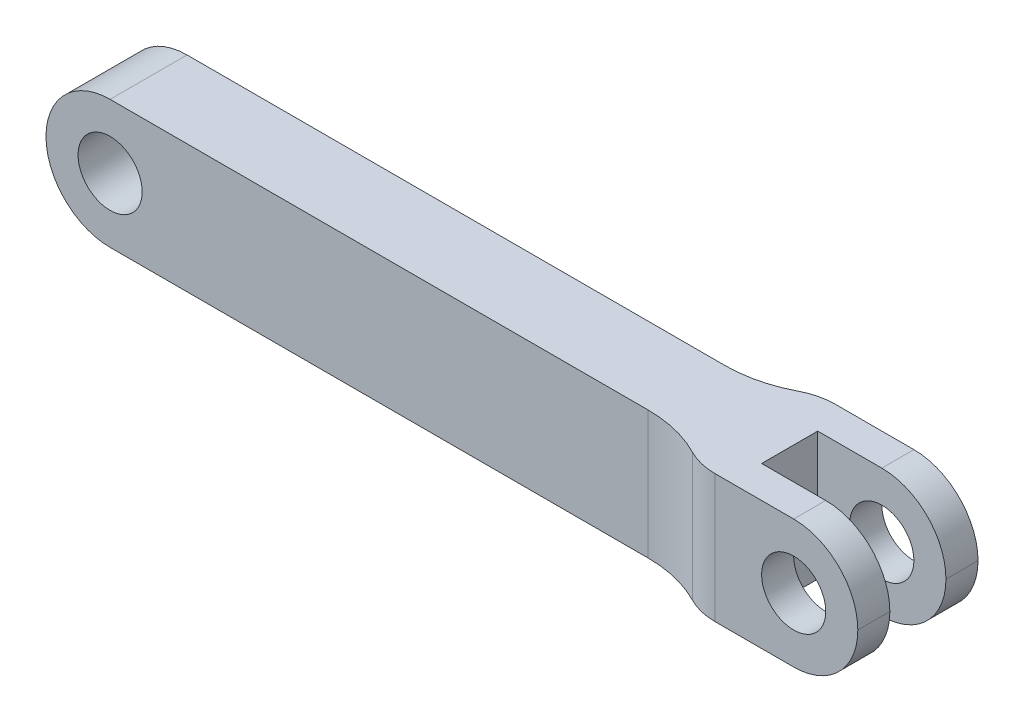
SolidWorks part; units mm, degrees
ref_plane "Piano frontale" through (0, 0, 0) normal (0, 0, 1) x (1, 0, 0)
ref_plane "Piano superiore" through (0, 0, 0) normal (0, 1, 0) x (1, 0, 0)
ref_plane "Piano destro" through (0, 0, 0) normal (1, 0, 0) x (0, 0, -1)
sketch "Schizzo1" plane through (0, 0, 0) normal (0, 0, 1) x (1, 0, 0)
  line L0 (0, 0) -> (100, 0) construction
  line L1 (0, 0) -> (100, 0) construction
  line L2 (0, 10) -> (100, 10)
  line L3 (0, -10) -> (100, -10)
  line L4 (100, -10) -> (100, 10)
  arc A0 (0, 10) -> (0, -10) centre (0, 0) ccw
  circle A2 centre (0, 0) radius 5
  point P3 (37.5, 0)
  dimension "D2" = 10
  dimension "D3" = 10
  dimension "D1" = 100
extrude "Estrusione-Estrusione1" add sketch "Schizzo1" along normal blind 12
sketch "Schizzo3" plane through (100, 0, 0) normal (1, 0, 0) x (0, 0, -1)
  line L0 (-6, 10) -> (-6, -10) construction
  line L1 (-12, 10) -> (0, 10) construction
  line L2 (-12, -10) -> (0, -10) construction
  line L3 (-15.375, 10) -> (-15.375, -10)
  line L4 (-1.625, 10) -> (3.375, 10)
  line L5 (-1.625, 10) -> (-1.625, -10)
  line L6 (-1.625, -10) -> (3.375, -10)
  line L7 (3.375, 10) -> (3.375, -10)
  line L8 (-10.375, -10) -> (-15.375, -10)
  line L9 (-10.375, 10) -> (-10.375, -10)
  line L10 (-10.375, 10) -> (-15.375, 10)
  dimension "D1" = 8.75
  dimension "D2" = 5
extrude "Estrusione-Estrusione2" add sketch "Schizzo3" along normal blind 20 and the other way blind 5
fillet "Raccordo1" radius 20 2 edges at (95, 0, 12) (95, 0, 0)
fillet "Raccordo2" radius 10 2 edges at (95, 0, 15.375) (95, 0, -3.375)
fillet "Raccordo3" radius 10 4 edges at (120, -10, 12.875) (120, 10, 12.875) (120, -10, -0.875) (120, 10, -0.875)
sketch "Schizzo4" plane through (0, 0, -3.375) normal (0, 0, -1) x (-1, 0, 0)
  line L0 (-120, 0) -> (-100, 0) construction
  circle A0 centre (-110, 0) radius 5
  dimension "D2" = 10
  dimension "D1" = 20
extrude "Taglio-Estrusione1" cut sketch "Schizzo4" against normal through all both
